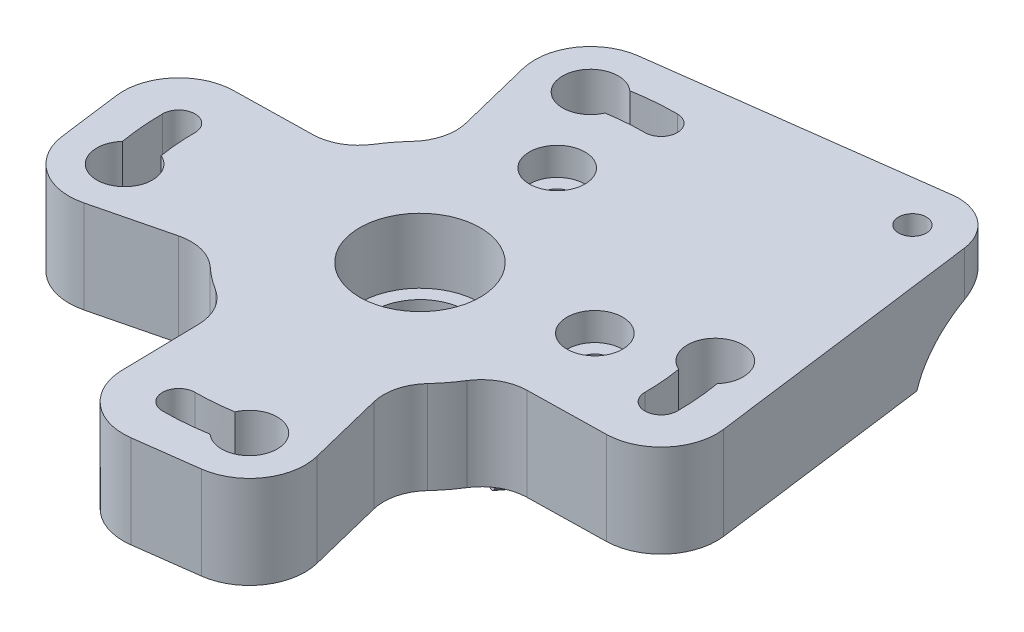
SolidWorks part; units mm, degrees
material "PLA"
ref_plane "Front Plane" through (0, 0, 0) normal (0, 0, 1) x (1, 0, 0)
ref_plane "Top Plane" through (0, 0, 0) normal (0, 1, 0) x (1, 0, 0)
ref_plane "Right Plane" through (0, 0, 0) normal (1, 0, 0) x (0, 0, -1)
sketch "Sketch1" plane through (0, 0, 0) normal (0, 1, 0) x (1, 0, 0)
  circle A0 centre (0, 0) radius 16
  circle A1 centre (0, 0) radius 5
  dimension "D1" = 32
  dimension "D2" = 10
extrude "Boss-Extrude1" add sketch "Sketch1" along normal blind 10
sketch "Sketch8" plane through (0, 10, 0) normal (0, 1, 0) x (1, 0, 0)
  circle A0 centre (0, 0) radius 6.5
  circle A1 centre (0, 0) radius 5 construction
  dimension "D1" = 1.5
extrude "Cut-Extrude7" cut sketch "Sketch8" against normal blind 7
sketch "Sketch2" plane through (0, 0, 0) normal (0, 1, 0) x (1, 0, 0)
  line L0 (-6.7293, 25.1141) -> (0, 0) construction
  line L5 (-7.5125, 31.0627) -> (-0.7832, 31.9487)
  line L6 (-12.5536, 23.6729) -> (-9.8214, 12.6309)
  line L7 (0, 0) -> (0, 26) construction
  line L8 (5.9989, 26.1154) -> (6.2176, 14.7425)
  line L9 (-9.8214, 12.6309) -> (6.2176, 14.7425)
  line L10 (-14.1655, 30.1869) -> (6.2176, 14.7425) construction
  line L11 (5.8698, 32.8246) -> (-9.8214, 12.6309) construction
  line L12 (-6.7293, 25.1141) -> (0, 26) construction
  circle A0 centre (0, 0) radius 6.5 construction
  circle A1 centre (0, 26) radius 3 construction
  circle A2 centre (-6.7293, 25.1141) radius 3
  arc A4 (-12.5536, 23.6729) -> (-7.5125, 31.0627) centre (-6.7293, 25.1141) cw
  arc A5 (-0.7832, 31.9487) -> (5.9989, 26.1154) centre (0, 26) cw
  circle A6 centre (0, 26) radius 1.75
  circle A7 centre (0, 0) radius 16 construction
  point P6 (-2.8449, 21.6092)
  dimension "D2" = 6
  dimension "D1" = 6
  dimension "D4" = 6
  dimension "D6" = 3.5
  dimension "D3" = 26
  dimension "D5" = 15
extrude "Boss-Extrude2" add sketch "Sketch2" along normal up to surface (10 mm away) up to face at (0, 10, 6.5)
sketch "Sketch5" plane through (0, 0, 0) normal (0, 1, 0) x (1, 0, 0)
  arc A0 (-6.7293, 25.1141) -> (0, 26) centre (0, 0) cw construction
  arc A1 (0, 27.75) -> (-7.1822, 26.8044) centre (0, 0) ccw
  arc A2 (0, 24.25) -> (-6.2764, 23.4237) centre (0, 0) ccw
  arc A3 (0, 24.25) -> (0, 27.75) centre (0, 26) ccw
  arc A4 (-7.1822, 26.8044) -> (-6.2764, 23.4237) centre (-6.7293, 25.1141) ccw
  circle A5 centre (0, 26) radius 1.75 construction
  point P5 (-3.3937, 25.7776)
extrude "Cut-Extrude5" cut sketch "Sketch5" along normal through all
sketch "Sketch6" plane through (0, 0, 0) normal (0, 1, 0) x (1, 0, 0)
  circle A0 centre (0, 26) radius 3
  arc A1 (-4.7236, 27.345) -> (-3.9764, 23.9218) centre (-6.7293, 25.1141) ccw construction
extrude "Cut-Extrude6" cut sketch "Sketch6" along normal blind 2.5
chamfer "Chamfer2" distance 1.75 angle 45 1 edges at (2.9967, 2.5, -26.1407)
fillet "Fillet1" radius 5 2 edges at (-9.8214, 5, -12.6309) (6.2176, 5, -14.7425)
pattern_circular "CirPattern1" count 4 over 360 about axis through (0, 10, 0) along (0, -1, 0) of "Boss-Extrude2", "Cut-Extrude5", "Cut-Extrude6", "Chamfer2", "Fillet1" reverse direction yes
sketch "Sketch9" plane through (0, 0, 0) normal (0, 1, 0) x (1, 0, 0)
  circle A0 centre (0, 0) radius 10
  circle A1 centre (0, 0) radius 22
  dimension "D1" = 20
  dimension "D2" = 44
extrude "Cut-Extrude8" cut sketch "Sketch9" along normal blind 6
fillet "Fillet2" radius 6 8 edges at (-11.3581, 3, -18.8413) (6.0946, 3, -21.139) (-18.8413, 3, 11.3581) (-21.139, 3, -6.0946) (21.139, 3, 6.0946) (18.8413, 3, -11.3581) (-6.0946, 3, 21.139) (11.3581, 3, 18.8413)
sketch "Sketch11" plane through (0, 10, 0) normal (0, 1, 0) x (1, 0, 0)
  line L4 (-1.4217, 16.2166) -> (16.032, 2.8239) construction
  line L6 (0, 0) -> (7.3051, 9.5202) construction
  line L7 (-5.5, 0) -> (5.5, 0) construction
  circle A3 centre (-1.4217, 16.2166) radius 1.5
  circle A4 centre (16.032, 2.8239) radius 1.5
  dimension "D2" = 52.5
  dimension "D4" = 3
  dimension "D1" = 22
  dimension "D3" = 12
extrude "Cut-Extrude9" cut sketch "Sketch11" against normal through all
sketch "Sketch12" plane through (0, 0, 0) normal (0, -1, 0) x (1, 0, 0)
  line L0 (-1.4043, -9.9009) -> (9.927, -1.206)
  line L1 (-1.4217, -16.2166) -> (16.032, -2.8239) construction
  circle A0 centre (0, 0) radius 10 construction
  circle A1 centre (0, 0) radius 10 construction
  circle A2 centre (0, 0) radius 5 construction
  arc A3 (-1.4043, -9.9009) -> (9.927, -1.206) centre (0, 0) ccw
  dimension "D1" = 7
extrude "Cut-Extrude10" cut sketch "Sketch12" against normal up to surface (6 mm away) up to face at (-1.4217, 6, -14.7166)
sketch "Sketch18" plane through (0, 10, 0) normal (0, 1, 0) x (1, 0, 0)
  line L0 (3.6526, 30.7601) -> (28.7666, 11.4894)
  arc A0 (5.9989, 26.1154) -> (-0.7832, 31.9487) centre (0, 26) ccw construction
  arc A1 (31.0627, 7.5125) -> (23.6729, 12.5536) centre (25.1141, 6.7293) ccw construction
sketch "Sketch16" plane through (4.2613, 0, -5.5535) normal (0.6088, 0, -0.7934) x (-0.7934, 0, -0.6088)
  line L0 (5.8831, 10) -> (1.5052, 10) construction
  line L2 (-10, 0) -> (-10, 10)
  line L3 (-10, 10) -> (10, 10)
  line L4 (10, 0) -> (10, 10)
  line L5 (-10, 0) -> (10, 0)
  line L7 (-7.1414, 0) -> (7.1414, 0) construction
  point P8 (0, 0)
  dimension "D1" = 20
extrude "Boss-Extrude8" add sketch "Sketch16" along normal up to vertex (19.6272 mm away) and the other way blind 7 up to point (28.7666, 10, -11.4894)
sketch "Sketch19" plane through (0, 10, 0) normal (0, 1, 0) x (1, 0, 0)
  circle A0 centre (0, 0) radius 5
  circle A1 centre (0, 0) radius 6.5
  circle A2 centre (0, 0) radius 5 construction
  circle A3 centre (0, 0) radius 6.5 construction
extrude "Cut-Extrude12" cut sketch "Sketch19" against normal through all contours A0
extrude "Cut-Extrude13" cut sketch "Sketch19<3>" against normal blind 7
sketch "Sketch19<3>" plane through (0, 10, 0) normal (0, 1, 0) x (1, 0, 0) same geometry as "Sketch19"
sketch "Sketch22" plane through (0, 6, 0) normal (0, -1, 0) x (1, 0, 0)
  line L0 (3.6526, -30.7601) -> (28.7666, -11.4894)
  line L1 (24.3458, 5.0621) -> (-11.1908, -22.2061)
  arc A0 (-0.7832, -31.9487) -> (5.9989, -26.1154) centre (0, -26) ccw construction
  arc A1 (23.6729, -12.5536) -> (31.0627, -7.5125) centre (25.1141, -6.7293) ccw construction
  arc A2 (26.1154, 5.9989) -> (21.9987, 0.2373) centre (27.9984, 0.302) ccw construction
  arc A3 (-5.9229, -21.1877) -> (-12.5536, -23.6729) centre (-7.5382, -26.9662) ccw construction
  arc A4 (-5.9229, -21.1877) -> (0.2373, -21.9987) centre (0, 0) ccw construction
  arc A5 (5.9989, -26.1154) -> (0.2373, -21.9987) centre (0.302, -27.9984) ccw construction
  arc A6 (21.1877, -5.9229) -> (23.6729, -12.5536) centre (26.9662, -7.5382) ccw construction
  arc A7 (21.1877, -5.9229) -> (21.9987, 0.2373) centre (0, 0) ccw construction
  arc A8 (-5.9229, -21.1877) -> (-11.1908, -22.2061) centre (-7.5382, -26.9662) ccw
  arc A9 (-5.9229, -21.1877) -> (0.2373, -21.9987) centre (0, 0) ccw
  arc A10 (5.9989, -26.1154) -> (0.2373, -21.9987) centre (0.302, -27.9984) ccw
  arc A11 (3.6526, -30.7601) -> (5.9989, -26.1154) centre (0, -26) ccw
  arc A12 (23.6729, -12.5536) -> (28.7666, -11.4894) centre (25.1141, -6.7293) ccw
  arc A13 (21.1877, -5.9229) -> (23.6729, -12.5536) centre (26.9662, -7.5382) ccw
  arc A14 (21.1877, -5.9229) -> (21.9987, 0.2373) centre (0, 0) ccw
  arc A15 (24.3458, 5.0621) -> (21.9987, 0.2373) centre (27.9984, 0.302) ccw
extrude "Boss-Extrude9" add sketch "Sketch22" along normal up to surface (6 mm away) and the other way up to surface (4 mm away) up to face at (3.4411, 0, 26.1377) other way up to face at (0, 10, 6.5)
sketch "Sketch21" plane through (0, 10, 0) normal (0, 1, 0) x (1, 0, 0)
  circle A0 centre (-1.4217, 16.2166) radius 1.5 construction
  circle A1 centre (16.032, 2.8239) radius 1.5 construction
  circle A2 centre (-1.4217, 16.2166) radius 1.5
  circle A3 centre (16.032, 2.8239) radius 1.5
extrude "Cut-Extrude15" cut sketch "Sketch21" against normal through all
sketch "Sketch20" plane through (0, 10, 0) normal (0, 1, 0) x (1, 0, 0)
  line L0 (16.2096, 21.1248) -> (0, 0) construction
  line L1 (3.6526, 30.7601) -> (28.7666, 11.4894) construction
  circle A0 centre (13.7746, 17.9514) radius 1.5
  dimension "D2" = 3
  dimension "D1" = 4
extrude "Cut-Extrude14" [suppressed] cut sketch "Sketch20" against normal through all
sketch "Sketch24" plane through (0, 10, 0) normal (0, 1, 0) x (1, 0, 0)
  line L0 (-0.7832, 31.9487) -> (22.4007, 35.0009)
  line L2 (31.0627, 7.5125) -> (28.0105, 30.6963)
  line L4 (3.6526, 30.7601) -> (28.7666, 11.4894) construction
  line L5 (3.6526, 30.7601) -> (28.7666, 11.4894)
  line L6 (16.2096, 21.1248) -> (27.3579, 35.6535) construction
  arc A0 (31.0627, 7.5125) -> (28.7666, 11.4894) centre (25.1141, 6.7293) ccw construction
  arc A1 (3.6526, 30.7601) -> (-0.7832, 31.9487) centre (0, 26) ccw construction
  arc A2 (31.0627, 7.5125) -> (28.7666, 11.4894) centre (25.1141, 6.7293) ccw
  arc A3 (3.6526, 30.7601) -> (-0.7832, 31.9487) centre (0, 26) ccw
  arc A4 (28.0105, 30.6963) -> (22.4007, 35.0009) centre (23.0533, 30.0437) ccw
  circle A5 centre (23.0533, 30.0437) radius 1.5
  line M39 (28.7666, 11.4894) -> (3.6526, 30.7601)
  arc M40 (3.6526, 30.7601) -> (-0.7832, 31.9487) centre (0, 26) ccw
  arc M66 (31.0627, 7.5125) -> (28.7666, 11.4894) centre (25.1141, 6.7293) ccw
  dimension "D1" = 5
  dimension "D2" = 3
extrude "Boss-Extrude11" add sketch "Sketch24" against normal up to surface (10 mm away) contours L6 L2 A4 A5 M39 M66 | L5 L6 A5 A4 L0 M40 region at (14.681, 10, -29.5906) region at (24.7826, 10, -21.8394) up to face at (3.4411, 0, 26.1377)
ref_plane "Plane1" through (4.2613, 0, -5.5535) normal (-0.6088, 0, 0.7934) x (0.7934, 0, 0.6088)
sketch "Sketch25" plane through (4.2613, 0, -5.5535) normal (-0.6088, 0, 0.7934) x (0.7934, 0, 0.6088)
  circle A0 centre (0, -2) radius 8
  dimension "D1" = 16
  dimension "D2" = 2
extrude "Cut-Extrude16" cut sketch "Sketch25" against normal through all
sketch "Sketch26" plane through (0, 6, 0) normal (0, -1, 0) x (1, 0, 0)
  line L10 (7.9335, 6.0876) -> (14.511, -2.4843)
  line L12 (26.1154, 5.9989) -> (17.693, 6.1609)
  line L13 (10.5303, 15.4956) -> (12.5536, 23.6729)
  line L14 (-5.9989, 26.1154) -> (-6.1609, 17.693)
  line L15 (-15.4956, 10.5303) -> (-23.6729, 12.5536)
  line L16 (-26.1154, -5.9989) -> (-17.693, -6.1609)
  line L17 (-10.5303, -15.4956) -> (-12.5536, -23.6729)
  line L19 (-1.356, -14.6596) -> (-7.9335, -6.0876)
  line L20 (7.9335, 6.0876) -> (14.511, -2.4843)
  line L22 (26.1154, 5.9989) -> (17.693, 6.1609)
  line L23 (10.5303, 15.4956) -> (12.5536, 23.6729)
  line L24 (-5.9989, 26.1154) -> (-6.1609, 17.693)
  line L25 (-15.4956, 10.5303) -> (-23.6729, 12.5536)
  line L26 (-26.1154, -5.9989) -> (-17.693, -6.1609)
  line L27 (-10.5303, -15.4956) -> (-12.5536, -23.6729)
  line L29 (-1.356, -14.6596) -> (-7.9335, -6.0876)
  line L31 (-1.4304, -14.7166) -> (-1.356, -14.6596)
  line L32 (16.0234, -1.3239) -> (24.3458, 5.0621)
  line L33 (16.0234, -1.3239) -> (24.3458, 5.0621)
  line L34 (-11.1908, -22.2061) -> (-2.8684, -15.82)
  line L35 (-11.1908, -22.2061) -> (-2.8684, -15.82)
  line L36 (-1.4304, -14.7166) -> (-1.356, -14.6596)
  line L38 (14.511, -2.4843) -> (14.5854, -2.4273)
  line L39 (14.511, -2.4843) -> (14.5854, -2.4273)
  arc A20 (-1.4304, -14.7166) -> (-2.8684, -15.82) centre (-1.4217, -16.2166) ccw
  arc A21 (26.1154, 5.9989) -> (24.3458, 5.0621) centre (27.9984, 0.302) ccw
  arc A22 (13.5537, 8.5028) -> (17.693, 6.1609) centre (17.7892, 11.16) ccw
  arc A23 (13.5537, 8.5028) -> (11.721, 10.8911) centre (0, 0) ccw
  arc A24 (10.5303, 15.4956) -> (11.721, 10.8911) centre (15.3839, 14.2946) ccw
  arc A25 (5.9229, 21.1877) -> (12.5536, 23.6729) centre (7.5382, 26.9662) ccw
  arc A26 (5.9229, 21.1877) -> (-0.2373, 21.9987) centre (0, 0) ccw
  arc A27 (-5.9989, 26.1154) -> (-0.2373, 21.9987) centre (-0.302, 27.9984) ccw
  arc A28 (-8.5028, 13.5537) -> (-6.1609, 17.693) centre (-11.16, 17.7892) ccw
  arc A29 (-8.5028, 13.5537) -> (-10.8911, 11.721) centre (0, 0) ccw
  arc A30 (-15.4956, 10.5303) -> (-10.8911, 11.721) centre (-14.2946, 15.3839) ccw
  arc A31 (-21.1877, 5.9229) -> (-23.6729, 12.5536) centre (-26.9662, 7.5382) ccw
  arc A32 (-21.1877, 5.9229) -> (-21.9987, -0.2373) centre (0, 0) ccw
  arc A33 (-26.1154, -5.9989) -> (-21.9987, -0.2373) centre (-27.9984, -0.302) ccw
  arc A34 (-13.5537, -8.5028) -> (-17.693, -6.1609) centre (-17.7892, -11.16) ccw
  arc A35 (-13.5537, -8.5028) -> (-11.721, -10.8911) centre (0, 0) ccw
  arc A36 (-10.5303, -15.4956) -> (-11.721, -10.8911) centre (-15.3839, -14.2946) ccw
  arc A37 (-11.1908, -22.2061) -> (-12.5536, -23.6729) centre (-7.5382, -26.9662) ccw
  arc A38 (-1.4304, -14.7166) -> (-2.8684, -15.82) centre (-1.4217, -16.2166) ccw
  arc A39 (7.9335, 6.0876) -> (-7.9335, -6.0876) centre (0, 0) ccw
  arc A41 (26.1154, 5.9989) -> (24.3458, 5.0621) centre (27.9984, 0.302) ccw
  arc A42 (13.5537, 8.5028) -> (17.693, 6.1609) centre (17.7892, 11.16) ccw
  arc A43 (13.5537, 8.5028) -> (11.721, 10.8911) centre (0, 0) ccw
  arc A44 (10.5303, 15.4956) -> (11.721, 10.8911) centre (15.3839, 14.2946) ccw
  arc A45 (5.9229, 21.1877) -> (12.5536, 23.6729) centre (7.5382, 26.9662) ccw
  arc A46 (5.9229, 21.1877) -> (-0.2373, 21.9987) centre (0, 0) ccw
  arc A47 (-5.9989, 26.1154) -> (-0.2373, 21.9987) centre (-0.302, 27.9984) ccw
  arc A48 (-8.5028, 13.5537) -> (-6.1609, 17.693) centre (-11.16, 17.7892) ccw
  arc A49 (-8.5028, 13.5537) -> (-10.8911, 11.721) centre (0, 0) ccw
  arc A50 (-15.4956, 10.5303) -> (-10.8911, 11.721) centre (-14.2946, 15.3839) ccw
  arc A51 (-21.1877, 5.9229) -> (-23.6729, 12.5536) centre (-26.9662, 7.5382) ccw
  arc A52 (-21.1877, 5.9229) -> (-21.9987, -0.2373) centre (0, 0) ccw
  arc A53 (-26.1154, -5.9989) -> (-21.9987, -0.2373) centre (-27.9984, -0.302) ccw
  arc A54 (-13.5537, -8.5028) -> (-17.693, -6.1609) centre (-17.7892, -11.16) ccw
  arc A55 (-13.5537, -8.5028) -> (-11.721, -10.8911) centre (0, 0) ccw
  arc A56 (-10.5303, -15.4956) -> (-11.721, -10.8911) centre (-15.3839, -14.2946) ccw
  arc A57 (-11.1908, -22.2061) -> (-12.5536, -23.6729) centre (-7.5382, -26.9662) ccw
  arc A59 (7.9335, 6.0876) -> (-7.9335, -6.0876) centre (0, 0) ccw
  arc A60 (16.0234, -1.3239) -> (14.5854, -2.4273) centre (16.032, -2.8239) ccw
  arc A61 (16.0234, -1.3239) -> (14.5854, -2.4273) centre (16.032, -2.8239) ccw
  dimension "D1" = 0
extrude "Boss-Extrude12" add sketch "Sketch26" along normal up to surface (6 mm away) up to face at (3.4411, 0, 26.1377)
ref_plane "Plane2" through (0, -2, 0) normal (0, 1, 0) x (1, 0, 0)
sketch "Sketch27" plane through (0, -2, 0) normal (0, 1, 0) x (1, 0, 0)
  line L0 (4.2613, 5.5535) -> (3.0438, 3.9668)
  line L1 (4.2613, 5.5535) -> (10.6082, 0.6834)
  line L2 (3.0438, 3.9668) -> (9.3906, -0.9033)
  line L3 (10.6082, 0.6834) -> (9.3906, -0.9033)
  line L4 (4.2613, 5.5535) -> (9.3906, -0.9033) construction
  line L5 (3.0438, 3.9668) -> (10.6082, 0.6834) construction
  line L6 (10.4066, 0.838) -> (-1.884, 10.2689) construction
  line L8 (-1.884, 10.2689) -> (10.4066, 0.838) construction
  circle A0 centre (0, 0) radius 5 construction
  point P6 (6.826, 2.3251)
  dimension "D1" = 8
revolve "Revolve1" add sketch "Sketch27" angle 180 about L0 reverse direction yes
sketch "Sketch29" plane through (0, -2, 0) normal (0, 1, 0) x (1, 0, 0)
  line L0 (10.6082, 0.6834) -> (-2.0855, 10.4236)
  line L1 (10.6082, 0.6834) -> (9.3906, -0.9033)
  line L2 (-2.0855, 10.4236) -> (-3.303, 8.8369)
  line L3 (9.3906, -0.9033) -> (-3.303, 8.8369)
  line L4 (10.6082, 0.6834) -> (-3.303, 8.8369) construction
  line L5 (-2.0855, 10.4236) -> (9.3906, -0.9033) construction
  line L8 (10.4066, 0.838) -> (-1.884, 10.2689) construction
  circle A0 centre (0, 0) radius 5 construction
  point P6 (3.6526, 4.7601)
  point P12 (4.2613, 5.5535)
  point P13 (4.2613, 5.5535)
  dimension "D1" = 16
extrude "Boss-Extrude13" add sketch "Sketch29" along normal up to surface (2 mm away) up to face at (-1.4217, 0, -14.7166)
sketch "Sketch30" plane through (0, 10, 0) normal (0, 1, 0) x (1, 0, 0)
  circle A0 centre (-1.4217, 16.2166) radius 3
  circle A1 centre (16.032, 2.8239) radius 3
  dimension "D1" = 6
extrude "Cut-Extrude17" cut sketch "Sketch30" against normal blind 3
